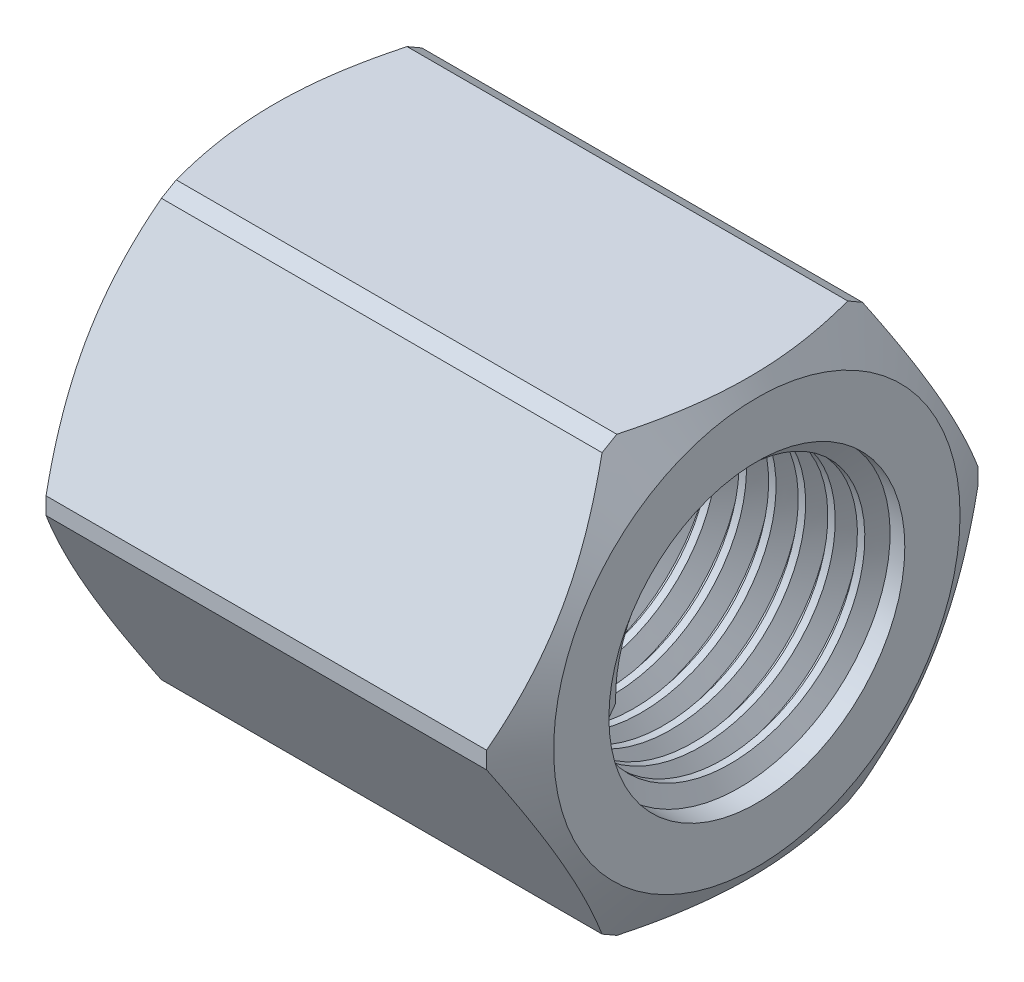
SolidWorks part; units mm, degrees
ref_plane "Спереди" through (0, 0, 0) normal (0, 0, 1) x (1, 0, 0)
ref_plane "Сверху" through (0, 0, 0) normal (0, 1, 0) x (1, 0, 0)
ref_plane "Справа" through (0, 0, 0) normal (1, 0, 0) x (0, 0, -1)
sketch "Эскиз1" plane through (0, 0, 0) normal (1, 0, 0) x (0, 0, -1)
  line L0 (0, 0) -> (33.8712, 0) construction
  line L1 (12.4517, 0.433) -> (6.6009, 10.567)
  line L2 (5.8509, 11) -> (-5.8509, 11)
  line L3 (-6.6009, 10.567) -> (-12.4517, 0.433)
  line L4 (-12.4517, -0.433) -> (-6.6009, -10.567)
  line L5 (-5.8509, -11) -> (5.8509, -11)
  line L6 (6.6009, -10.567) -> (12.4517, -0.433)
  line L7 (6.6009, 10.567) -> (5.8509, 11)
  line L8 (-5.8509, 11) -> (-6.6009, 10.567)
  line L9 (-12.4517, 0.433) -> (-12.4517, -0.433)
  line L10 (-6.6009, -10.567) -> (-5.8509, -11)
  line L11 (5.8509, -11) -> (6.6009, -10.567)
  line L12 (12.4517, -0.433) -> (12.4517, 0.433)
  circle A0 centre (0, 0) radius 11 construction
  circle A1 centre (0, 0) radius 3.5
  point P2 (12.7017, 0)
  point P3 (6.3509, 11)
  point P4 (-6.3509, 11)
  point P5 (-12.7017, 0)
  point P6 (-6.3509, -11)
  point P7 (6.3509, -11)
  dimension "D2" = 7
  dimension "D1" = 22
extrude "Бобышка-Вытянуть1" add sketch "Эскиз1" along normal blind 25
sketch "Эскиз9" plane through (25, 0, 0) normal (1, 0, 0) x (0, 0, -1)
  circle A0 centre (0, 0) radius 7.5
  dimension "D1" = 15
extrude "Вырез-Вытянуть2" cut sketch "Эскиз9" against normal blind 20
thread "Резьба1" pitch 1.5 method extrude profile "Профиль резьбы2" start angle 0, offset 0, length 0, pitch 1.5, diameter 15
ref_plane "Плоскость5" through (25, 0, 7.5) normal (0, -1, 0) x (0, 0, 1)
sketch "Профиль резьбы2" plane through (25, 0, 7.5) normal (0, -1, 0) x (0, 0, 1)
  line L0 (0, 0) -> (0, 1.5) construction
  line L11 (0, 0) -> (0, 1.3125)
  line L12 (0, 1.3125) -> (-0.8119, 0.8437)
  line L13 (-0.8119, 0.8437) -> (-0.8119, 0.4687)
  line L15 (-0.8119, 0.4687) -> (0, 0)
  line L17 (-0.8119, 0.6562) -> (0, 0.6562) construction
  point P2 (0, 0)
  dimension "Pitch" = 1.5
  dimension "Profile_Angle" = 60
  dimension "Profile_Land" = 0.375
  dimension "Profile_Height" = 0.8119
sketch "Эскиз14" plane through (0, 0, 0) normal (-1, 0, 0) x (0, 0, 1)
  line L0 (6.6009, 10.567) -> (12.4517, 0.433) construction
  circle A0 centre (0, 0) radius 10.5
  dimension "D1" = 0.5
sketch "Эскиз15" plane through (0, 0, 0) normal (0, 1, 0) x (1, 0, 0)
  line L0 (0, 10) -> (0, 14)
  line L1 (0, 10.5) -> (0, -10.5) construction
  line L2 (0, 14) -> (2.3094, 14)
  line L3 (2.3094, 14) -> (0, 10)
  line L4 (25.256, 14) -> (25.256, 9.8569)
  line L5 (25.256, 9.8569) -> (22.8639, 14)
  line L6 (22.8639, 14) -> (25.256, 14)
  point P8 (0, 0)
  point P10 (0, 0)
  dimension "D1" = 30
  dimension "D2" = 4
  dimension "D3" = 10
  dimension "D4" = 30
sweep "Вырез-По траектории1" cut profiles "Эскиз15" path "Эскиз14"
ref_axis "Ось1" through (5, 0, 0) along (-1, 0, 0)
